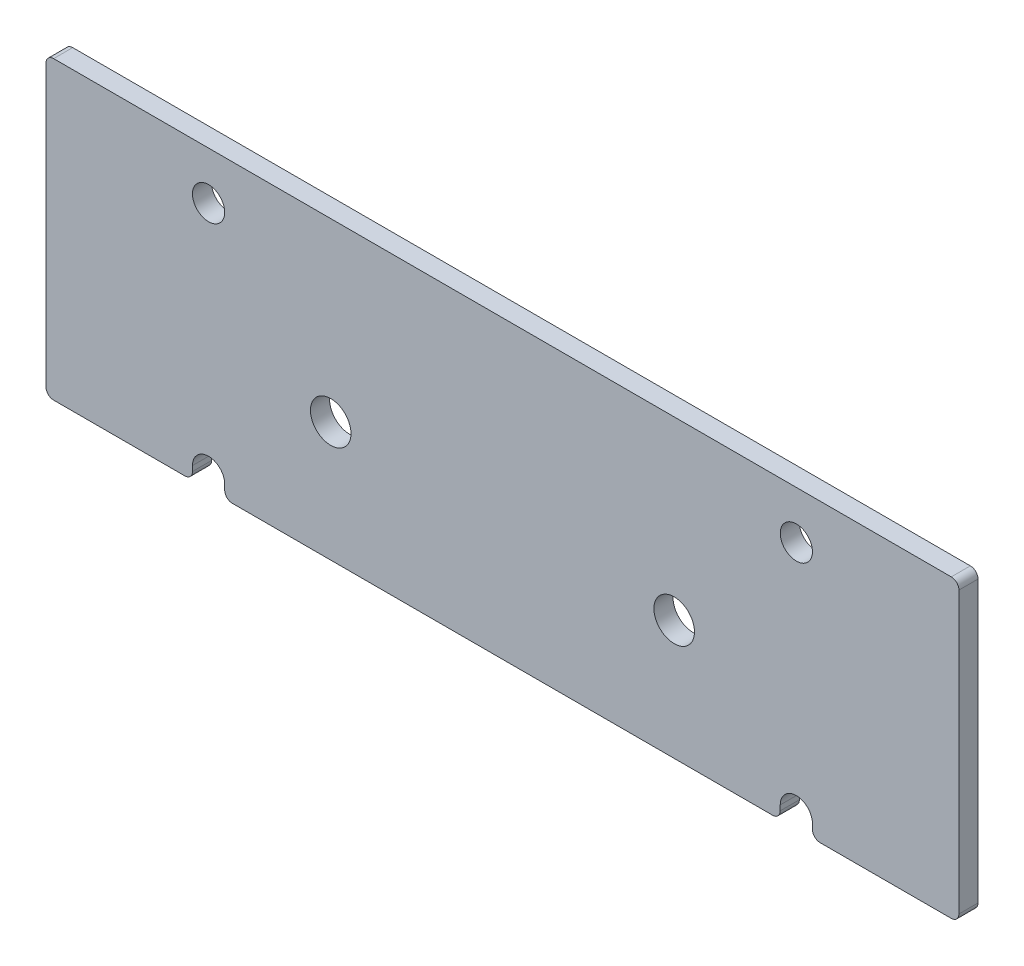
SolidWorks part; units mm, degrees
material "Plain Carbon Steel"
ref_plane "Front Plane" through (0, 0, 0) normal (0, 0, 1) x (1, 0, 0)
ref_plane "Top Plane" through (0, 0, 0) normal (0, 1, 0) x (1, 0, 0)
ref_plane "Right Plane" through (0, 0, 0) normal (1, 0, 0) x (0, 0, -1)
sketch "Sketch1" plane through (0, 0, 0) normal (0, 0, 1) x (1, 0, 0)
  line L0 (127, 0) -> (-127, 0) construction
  line L1 (101.6, -357.1875) -> (101.6, 357.1875) construction
  line L2 (152.4, 0) -> (152.4, 357.1875) construction
  line L3 (-101.6, -357.1875) -> (-101.6, 357.1875) construction
  line L4 (-152.4, -357.1875) -> (-152.4, 357.1875) construction
  line L5 (101.6, 59.0332) -> (-101.6, 262.2332) construction
  line L6 (101.6, 94.9543) -> (-101.6, 298.1543) construction
  line L7 (0, 196.5543) -> (0, 160.6332) construction
  line L8 (0, 178.5938) -> (152.4, 178.5938) construction
  line L9 (105.003, 12.7) -> (-105.003, 12.7) construction
  line L10 (105.003, -12.7) -> (-105.003, -12.7) construction
  line L11 (-101.6, 59.0332) -> (101.6, 262.2332) construction
  line L12 (-101.6, 94.9543) -> (101.6, 298.1543) construction
  line L13 (152.4, 0) -> (152.4, -357.1875) construction
  line L14 (-101.6, -94.9543) -> (101.6, -298.1543) construction
  line L15 (-101.6, -59.0332) -> (101.6, -262.2332) construction
  line L16 (101.6, -94.9543) -> (-101.6, -298.1543) construction
  line L17 (101.6, -59.0332) -> (-101.6, -262.2332) construction
  line L18 (-179.07, -25.4) -> (-179.07, 128.4583)
  line L19 (-179.07, 128.4583) -> (179.07, 128.4583)
  line L20 (179.07, 128.4583) -> (179.07, -25.4)
  line L21 (179.07, -25.4) -> (153.67, -25.4)
  line L22 (153.67, -25.4) -> (153.67, -1.27)
  line L23 (100.33, -1.27) -> (100.33, -25.4)
  line L24 (100.33, -25.4) -> (-100.33, -25.4)
  line L25 (-100.33, -25.4) -> (-100.33, -1.27)
  line L26 (-153.67, -1.27) -> (-153.67, -25.4)
  line L27 (-179.07, -25.4) -> (-153.67, -25.4)
  circle A0 centre (-127, 0) radius 25.4 construction
  circle A1 centre (127, 0) radius 25.4 construction
  circle A2 centre (-127, 357.1875) radius 25.4 construction
  circle A3 centre (127, 357.1875) radius 25.4 construction
  arc A4 (100.33, -1.27) -> (153.67, -1.27) centre (127, -1.27) cw
  arc A5 (-100.33, -1.27) -> (-153.67, -1.27) centre (-127, -1.27) ccw
  circle A6 centre (96.139, 108.1383) radius 5.461 construction
  point P23 (0, 178.5938)
  point P33 (101.6, 0)
  point P37 (-152.4, 0)
  point P38 (-101.6, 0)
  point P53 (127, 25.4)
  point P54 (127, 25.4)
  dimension "D2" = 50.8
  dimension "D7" = 26.67
  dimension "D9" = 25.4
  dimension "D10" = 10.922
  dimension "D1" = 254
  dimension "D3" = 357.1875
  dimension "D4" = 25.4
  dimension "D5" = 45
  dimension "D6" = 25.4
  dimension "D8" = 25.4
  dimension "D11" = 20.32
extrude "Boss-Extrude1" add sketch "Sketch1" along normal blind 6.35
sketch "Sketch9" plane through (0, 0, 6.35) normal (0, 0, 1) x (1, 0, 0)
  line L0 (-151.892, 128.4583) -> (-151.892, 8.3048)
  line L2 (-152.4, -357.1875) -> (-152.4, 357.1875) construction
  line L3 (179.07, 128.4583) -> (-179.07, 128.4583) construction
  line L4 (-151.892, 128.4583) -> (-179.07, 128.4583)
  line L5 (-179.07, 128.4583) -> (-179.07, -25.4)
  line L6 (-179.07, -25.4) -> (-153.67, -25.4)
  line L7 (-179.07, -25.4) -> (-153.67, -25.4) construction
  line L8 (-153.67, -25.4) -> (-153.67, -1.27) construction
  line L9 (-153.67, -25.4) -> (-153.67, -1.27)
  line L10 (0, 0) -> (0, 128.4583) construction
  line L11 (153.67, -25.4) -> (153.67, -1.27)
  line L12 (179.07, -25.4) -> (153.67, -25.4)
  line L13 (179.07, 128.4583) -> (179.07, -25.4)
  line L14 (151.892, 128.4583) -> (179.07, 128.4583)
  line L15 (151.892, 128.4583) -> (151.892, 8.3048)
  arc A0 (-100.33, -1.27) -> (-153.67, -1.27) centre (-127, -1.27) ccw construction
  arc A1 (-153.67, -1.27) -> (-151.892, 8.3048) centre (-127, -1.27) cw
  arc A2 (153.67, -1.27) -> (151.892, 8.3048) centre (127, -1.27) ccw
  dimension "D1" = 0.508
extrude "Cut-Extrude3" cut sketch "Sketch9" against normal through all
hole_wizard "27/64 (0.42188) Diameter Hole1" positions "Sketch2" profile "Sketch3" hole size "27/64" standard "ANSI Inch" end condition through all
sketch "Sketch2" plane through (0, 0, 6.35) normal (0, 0, 1) x (1, 0, 0)
  line L0 (-127, 0) -> (-127, 128.4583) construction
  line L1 (-179.07, 128.4583) -> (179.07, 128.4583) construction
  line L2 (0, 128.4583) -> (0, -25.4) construction
  line L3 (100.33, -25.4) -> (-100.33, -25.4) construction
  line L4 (-101.6, -357.1875) -> (-101.6, 357.1875) construction
  line L5 (151.892, 128.4583) -> (-151.892, 128.4583) construction
  point P0 (-97.79, 34.29)
  point P2 (-97.79, 112.5833)
  point P19 (97.79, 34.29)
  point P22 (97.79, 112.5833)
  point P25 (0, 0)
  point P26 (0, 0)
  point P27 (0, 0)
  point P28 (0, 0)
  dimension "D1" = 15.875
  dimension "D2" = 3.81
  dimension "D3" = 34.29
sketch "Sketch3" plane through (-97.79, 34.29, 6.35) normal (1, 0, 0) x (0, -1, 0)
  line L0 (0, 0) -> (0, 6.35)
  line L1 (0, 6.35) -> (5.3579, 6.35)
  line L2 (5.3579, 6.35) -> (5.3579, 0)
  line L5 (5.3579, 0) -> (0, 0)
  line L11 (0, -6.35) -> (0, 107.95) construction
  dimension "Thru Hole Dia." = 10.7158
  dimension "Thru Hole Depth" = 6.35
fillet "Fillet1" radius 2.54 6 edges at (100.33, -25.4, 3.175) (-100.33, -25.4, 3.175) (151.892, 8.3048, 3.175) (151.892, 128.4583, 3.175) (-151.892, 128.4583, 3.175) (-151.892, 8.3048, 3.175)
hole_wizard "1/2 Clearance Hole1" positions "Sketch4" profile "Sketch5" hole size "1/2" standard "ANSI Inch" end condition through all
sketch "Sketch4" plane through (0, 0, 6.35) normal (0, 0, 1) x (1, 0, 0)
  line L1 (0, 0) -> (0, 160.6332) construction
  line L2 (127, 0) -> (-127, 0) construction
  line L4 (105.003, 12.7) -> (-105.003, 12.7) construction
  line L5 (101.6, -357.1875) -> (101.6, 357.1875) construction
  circle A0 centre (57.15, 69.85) radius 12.7 construction
  point P0 (57.15, 69.85)
  point P18 (-57.15, 69.85)
  dimension "D1" = 25.4
  dimension "D2" = 57.15
  dimension "D3" = 44.45
sketch "Sketch5" plane through (57.15, 69.85, 6.35) normal (1, 0, 0) x (0, -1, 0)
  line L0 (0, 0) -> (0, 6.35)
  line L1 (0, 6.35) -> (6.7462, 6.35)
  line L2 (6.7462, 6.35) -> (6.7462, 0)
  line L5 (6.7462, 0) -> (0, 0)
  line L11 (0, -6.35) -> (0, 107.95) construction
  dimension "Thru Hole Dia." = 13.4925
  dimension "Thru Hole Depth" = 6.35
sketch "Sketch6" plane through (0, 0, 6.35) normal (0, 0, 1) x (1, 0, 0)
  line L0 (-117.8622, 128.4583) -> (-117.8622, 23.7857) construction
  line L1 (149.352, 128.4583) -> (-149.352, 128.4583) construction
  arc A0 (-100.33, -1.27) -> (-147.4083, 15.8994) centre (-127, -1.27) ccw construction
ref_plane "Plane1" through (-117.8622, 0, 0) normal (1, 0, 0) x (0, 0, -1)
sketch "Sketch7" plane through (0, 0, 6.35) normal (0, 0, 1) x (1, 0, 0)
  line L0 (-151.892, 30.0333) -> (151.892, 30.0333)
  line L3 (-151.892, 30.0333) -> (-151.892, -25.4)
  line L4 (-151.892, -25.4) -> (151.892, -25.4)
  line L5 (151.892, -25.4) -> (151.892, 30.0333)
  line L6 (-97.79, -25.4) -> (97.79, -25.4) construction
  line L7 (149.352, 128.4583) -> (-149.352, 128.4583) construction
  line L8 (-151.892, 17.5346) -> (-151.892, 125.9183) construction
  line L9 (151.892, 125.9183) -> (151.892, 17.5346) construction
  point P2 (-151.892, 30.0333)
  point P4 (151.892, 30.0333)
  dimension "D1" = 98.425
extrude "Cut-Extrude1" cut sketch "Sketch7" against normal through all
sketch "Sketch8" plane through (0, 0, 6.35) normal (0, 0, 1) x (1, 0, 0)
  line L4 (-101.0438, 30.0333) -> (-151.892, 30.0333) construction
  line L8 (-126.4679, 30.0333) -> (-126.4679, 128.4583) construction
  line L9 (-101.0438, 30.0333) -> (-151.892, 30.0333) construction
  line L10 (149.352, 128.4583) -> (-149.352, 128.4583) construction
  line L11 (-94.5362, 30.0333) -> (-92.4321, 30.0333)
  line L12 (-92.4321, 34.29) -> (-94.5362, 30.0333)
  line L13 (-92.4321, 34.29) -> (-92.4321, 30.0333)
  line L14 (-103.1479, 34.29) -> (-103.1479, 30.0333)
  line L15 (-103.1479, 34.29) -> (-101.0438, 30.0333)
  line L16 (-101.0438, 30.0333) -> (-103.1479, 30.0333)
  line L17 (0, 30.0333) -> (0, 128.4583) construction
  line L18 (94.5362, 30.0333) -> (-94.5362, 30.0333) construction
  line L25 (101.0438, 30.0333) -> (103.1479, 30.0333)
  line L26 (103.1479, 34.29) -> (101.0438, 30.0333)
  line L27 (103.1479, 34.29) -> (103.1479, 30.0333)
  line L28 (92.4321, 34.29) -> (92.4321, 30.0333)
  line L29 (92.4321, 34.29) -> (94.5362, 30.0333)
  line L30 (94.5362, 30.0333) -> (92.4321, 30.0333)
  line L31 (-97.79, 34.29) -> (-97.79, 39.6479) construction
  arc A1 (-94.5362, 30.0333) -> (-101.0438, 30.0333) centre (-97.79, 34.29) ccw construction
  arc A2 (-94.5362, 30.0333) -> (-101.0438, 30.0333) centre (-97.79, 34.29) ccw construction
  point P0 (-90.2514, 30.0333)
extrude "Cut-Extrude2" cut sketch "Sketch8" against normal through all
fillet "Fillet2" radius 2.54 6 edges at (-103.1479, 30.0333, 3.175) (-92.4321, 30.0333, 3.175) (92.4321, 30.0333, 3.175) (103.1479, 30.0333, 3.175) (151.892, 30.0333, 3.175) (-151.892, 30.0333, 3.175)
